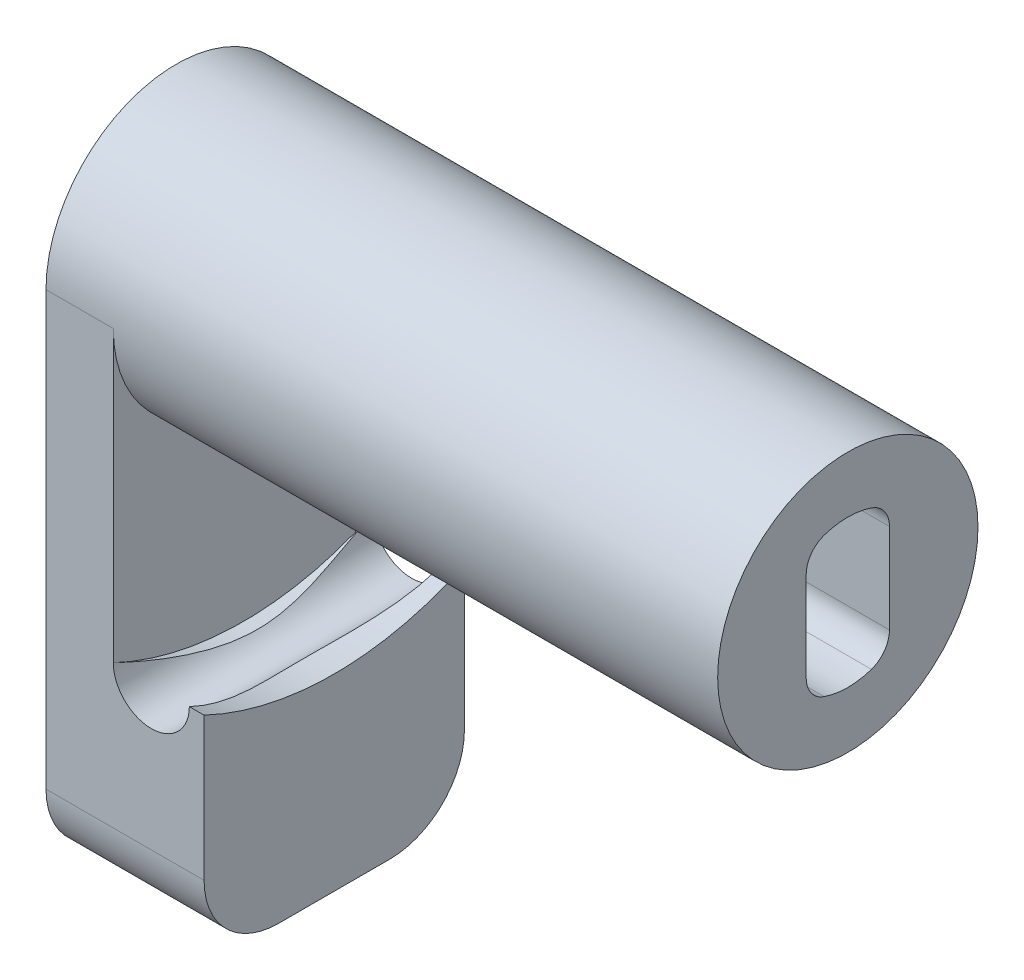
SolidWorks part; units mm, degrees
material "ABS"
ref_plane "Front Plane" through (0, 0, 0) normal (1, 0, 0) x (0, 1, 0)
ref_plane "Top Plane" through (0, 0, 0) normal (0, 0, 1) x (0, 1, 0)
ref_plane "Right Plane" through (0, 0, 0) normal (0, 1, 0) x (-1, 0, 0)
sketch "Sketch1" plane through (0, 0, 0) normal (1, 0, 0) x (0, 1, 0)
  circle A2 centre (0, 0) radius 8.7376
  dimension "D3" = 17.4752
extrude "Boss-Extrude1" add sketch "Sketch1" along normal blind 45.085 contours A2 region at (0, 0, 0)
sketch "Sketch10" plane through (0, 0, 0) normal (-1, 0, 0) x (0, -1, 0)
  line L0 (0, 8.7376) -> (34.036, 8.7376)
  line L2 (34.036, 8.7376) -> (34.036, -8.7376)
  line L3 (34.036, -8.7376) -> (0, -8.7376)
  circle A0 centre (0, 0) radius 8.7376 construction
  arc A2 (0, 8.7376) -> (0, -8.7376) centre (0, 0) cw
  dimension "D1" = 34.036
extrude "Boss-Extrude3" add sketch "Sketch10" against normal blind 4.516 contours L0 A2 L3 L2 region at (0, -20.3793, 0)
fillet "Fillet2" radius 5 2 edges at (2.258, -34.036, 8.7376) (2.258, -34.036, -8.7376)
sketch "Sketch14" [suppressed] plane through (0, 0, 0) normal (-1, 0, 0) x (0, 0, 1)
  line L0 (0.5115, -3.4237) -> (0.3944, -4.0089)
  line L1 (0, 0) -> (0, -4.064) construction
  line L2 (0, 0) -> (0.5606, -3.4335) construction
  line L3 (0.6039, -3.4087) -> (0.9011, -3.9262)
  line L4 (-0.6903, -3.3922) -> (-1.0005, -3.9021)
  line L5 (-0.5983, -3.4096) -> (-0.4961, -3.9976)
  line L6 (-1.8089, -2.9515) -> (-2.2748, -3.3245)
  line L7 (-1.7284, -2.9994) -> (-1.8334, -3.5869)
  line L8 (-2.7093, -2.1549) -> (-3.2746, -2.346)
  line L9 (-2.65, -2.2273) -> (-2.9496, -2.7435)
  line L10 (-3.2829, -1.0983) -> (-3.8795, -1.0846)
  line L11 (-3.252, -1.1867) -> (-3.7101, -1.5692)
  line L12 (-3.4605, 0.0907) -> (-4.0165, 0.3077)
  line L13 (-3.4617, -0.0029) -> (-4.023, -0.2057)
  line L14 (-3.2208, 1.2689) -> (-3.669, 1.6629)
  line L15 (-3.2539, 1.1813) -> (-3.8507, 1.1827)
  line L16 (-2.5926, 2.2939) -> (-2.879, 2.8175)
  line L17 (-2.6537, 2.223) -> (-3.214, 2.4284)
  line L18 (-1.6517, 3.0423) -> (-1.7417, 3.6323)
  line L19 (-1.7333, 2.9965) -> (-2.1896, 3.3812)
  line L20 (-0.5115, 3.4237) -> (-0.3944, 4.0089)
  line L21 (-0.6039, 3.4087) -> (-0.9011, 3.9262)
  line L22 (0.6903, 3.3922) -> (1.0005, 3.9021)
  line L23 (0.5983, 3.4096) -> (0.4961, 3.9976)
  line L24 (1.8089, 2.9515) -> (2.2748, 3.3245)
  line L25 (1.7284, 2.9994) -> (1.8334, 3.5869)
  line L26 (2.7093, 2.1549) -> (3.2746, 2.346)
  line L27 (2.65, 2.2273) -> (2.9496, 2.7435)
  line L28 (3.2829, 1.0983) -> (3.8795, 1.0846)
  line L29 (3.252, 1.1867) -> (3.7101, 1.5692)
  line L30 (3.4605, -0.0907) -> (4.0165, -0.3077)
  line L31 (3.4617, 0.0029) -> (4.023, 0.2057)
  line L32 (3.2208, -1.2689) -> (3.669, -1.6629)
  line L33 (3.2539, -1.1813) -> (3.8507, -1.1827)
  line L34 (2.5926, -2.2939) -> (2.879, -2.8175)
  line L35 (2.6537, -2.223) -> (3.214, -2.4284)
  line L36 (1.6517, -3.0423) -> (1.7417, -3.6323)
  line L37 (1.7333, -2.9965) -> (2.1896, -3.3812)
  line L38 (-0.1032, -4.0627) -> (0, -4.064)
  line L39 (-1.4865, -3.7824) -> (-1.39, -3.8189)
  line L40 (-2.6905, -3.0459) -> (-2.6123, -3.1132)
  line L41 (-3.5195, -2.032) -> (-3.57, -1.942)
  line L42 (-4.0023, -0.7057) -> (-4.0189, -0.6039)
  line L43 (-4.0023, 0.7057) -> (-3.9831, 0.8071)
  line L44 (-3.5195, 2.032) -> (-3.4668, 2.1207)
  line L45 (-2.6123, 3.1132) -> (-2.5324, 3.1785)
  line L46 (-1.39, 3.8189) -> (-1.2926, 3.853)
  line L47 (0, 4.064) -> (0.1032, 4.0627)
  line L48 (1.39, 3.8189) -> (1.4865, 3.7824)
  line L49 (2.6123, 3.1132) -> (2.6905, 3.0459)
  line L50 (3.5195, 2.032) -> (3.57, 1.942)
  line L51 (4.0023, 0.7057) -> (4.0189, 0.6039)
  line L52 (4.0023, -0.7057) -> (3.9831, -0.8071)
  line L53 (3.5195, -2.032) -> (3.4668, -2.1207)
  line L54 (2.6123, -3.1132) -> (2.5324, -3.1785)
  line L55 (1.39, -3.8189) -> (1.2926, -3.853)
  arc A0 (0.3497, -4.0489) -> (0, -4.064) centre (0, 0) cw
  arc A1 (0.3497, -4.0489) -> (0.3944, -4.0089) centre (0.3454, -3.9991) ccw
  arc A2 (0.5115, -3.4237) -> (0.6039, -3.4087) centre (0.5606, -3.4335) cw
  arc A3 (0.4203, -4.0631) -> (0.3944, -4.0089) centre (0.4434, -4.0187) cw
  arc A4 (0.4203, -4.0631) -> (0.7372, -4.2116) centre (2.3016, -0.4608) ccw
  arc A6 (0.9562, -3.9499) -> (0.9011, -3.9262) centre (0.9445, -3.9013) cw
  arc A7 (0.9562, -3.9499) -> (1.2926, -3.853) centre (0, 0) ccw
  arc A8 (-1.0562, -3.9243) -> (-1.39, -3.8189) centre (0, 0) cw
  arc A9 (-1.0562, -3.9243) -> (-1.0005, -3.9021) centre (-1.0432, -3.8761) ccw
  arc A10 (-0.6903, -3.3922) -> (-0.5983, -3.4096) centre (-0.6476, -3.4182) cw
  arc A11 (-0.4524, -4.0387) -> (-0.4961, -3.9976) centre (-0.4468, -3.9891) cw
  arc A12 (-0.4524, -4.0387) -> (-0.1032, -4.0627) centre (0, 0) ccw
  arc A13 (-2.3347, -3.3264) -> (-2.6123, -3.1132) centre (0, 0) cw
  arc A14 (-2.3347, -3.3264) -> (-2.2748, -3.3245) centre (-2.306, -3.2855) ccw
  arc A15 (-1.8089, -2.9515) -> (-1.7284, -2.9994) centre (-1.7776, -2.9906) cw
  arc A16 (-1.8064, -3.6405) -> (-1.8334, -3.5869) centre (-1.7842, -3.5957) cw
  arc A17 (-1.8064, -3.6405) -> (-1.4865, -3.7824) centre (0, 0) ccw
  arc A18 (-3.3316, -2.3273) -> (-3.5195, -2.032) centre (0, 0) cw
  arc A19 (-3.3316, -2.3273) -> (-3.2746, -2.346) centre (-3.2906, -2.2987) ccw
  arc A20 (-2.7093, -2.1549) -> (-2.65, -2.2273) centre (-2.6933, -2.2022) cw
  arc A21 (-2.9426, -2.8031) -> (-2.9496, -2.7435) centre (-2.9064, -2.7686) cw
  arc A22 (-2.9426, -2.8031) -> (-2.6905, -3.0459) centre (0, 0) ccw
  arc A23 (-3.9267, -1.0475) -> (-4.0023, -0.7057) centre (0, 0) cw
  arc A24 (-3.9267, -1.0475) -> (-3.8795, -1.0846) centre (-3.8784, -1.0346) ccw
  arc A25 (-3.2829, -1.0983) -> (-3.252, -1.1867) centre (-3.284, -1.1483) cw
  arc A26 (-3.7238, -1.6276) -> (-3.7101, -1.5692) centre (-3.678, -1.6076) cw
  arc A27 (-3.7238, -1.6276) -> (-3.57, -1.942) centre (0, 0) ccw
  arc A28 (-4.0481, 0.3587) -> (-4.0023, 0.7057) centre (0, 0) cw
  arc A29 (-4.0481, 0.3587) -> (-4.0165, 0.3077) centre (-3.9983, 0.3543) ccw
  arc A30 (-3.4605, 0.0907) -> (-3.4617, -0.0029) centre (-3.4787, 0.0442) cw
  arc A31 (-4.0559, -0.2558) -> (-4.023, -0.2057) centre (-4.006, -0.2527) cw
  arc A32 (-4.0559, -0.2558) -> (-4.0189, -0.6039) centre (0, 0) ccw
  arc A33 (-3.6813, 1.7216) -> (-3.5195, 2.032) centre (0, 0) cw
  arc A34 (-3.6813, 1.7216) -> (-3.669, 1.6629) centre (-3.636, 1.7005) ccw
  arc A35 (-3.2208, 1.2689) -> (-3.2539, 1.1813) centre (-3.2538, 1.2313) cw
  arc A36 (-3.8988, 1.1468) -> (-3.8507, 1.1827) centre (-3.8509, 1.1327) cw
  arc A37 (-3.8988, 1.1468) -> (-3.9831, 0.8071) centre (0, 0) ccw
  arc A38 (-2.8705, 2.8769) -> (-2.6123, 3.1132) centre (0, 0) cw
  arc A39 (-2.8705, 2.8769) -> (-2.879, 2.8175) centre (-2.8352, 2.8415) ccw
  arc A40 (-2.5926, 2.2939) -> (-2.6537, 2.223) centre (-2.6365, 2.2699) cw
  arc A41 (-3.2715, 2.4111) -> (-3.214, 2.4284) centre (-3.2312, 2.3815) cw
  arc A42 (-3.2715, 2.4111) -> (-3.4668, 2.1207) centre (0, 0) ccw
  arc A43 (-1.7134, 3.6852) -> (-1.39, 3.8189) centre (0, 0) cw
  arc A44 (-1.7134, 3.6852) -> (-1.7417, 3.6323) centre (-1.6923, 3.6398) ccw
  arc A45 (-1.6517, 3.0423) -> (-1.7333, 2.9965) centre (-1.7011, 3.0348) cw
  arc A46 (-2.2495, 3.3846) -> (-2.1896, 3.3812) centre (-2.2218, 3.343) cw
  arc A47 (-2.2495, 3.3846) -> (-2.5324, 3.1785) centre (0, 0) ccw
  arc A48 (-0.3497, 4.0489) -> (0, 4.064) centre (0, 0) cw
  arc A49 (-0.3497, 4.0489) -> (-0.3944, 4.0089) centre (-0.3454, 3.9991) ccw
  arc A50 (-0.5115, 3.4237) -> (-0.6039, 3.4087) centre (-0.5606, 3.4335) cw
  arc A51 (-0.9562, 3.9499) -> (-0.9011, 3.9262) centre (-0.9445, 3.9013) cw
  arc A52 (-0.9562, 3.9499) -> (-1.2926, 3.853) centre (0, 0) ccw
  arc A53 (1.0562, 3.9243) -> (1.39, 3.8189) centre (0, 0) cw
  arc A54 (1.0562, 3.9243) -> (1.0005, 3.9021) centre (1.0432, 3.8761) ccw
  arc A55 (0.6903, 3.3922) -> (0.5983, 3.4096) centre (0.6476, 3.4182) cw
  arc A56 (0.4524, 4.0387) -> (0.4961, 3.9976) centre (0.4468, 3.9891) cw
  arc A57 (0.4524, 4.0387) -> (0.1032, 4.0627) centre (0, 0) ccw
  arc A58 (2.3347, 3.3264) -> (2.6123, 3.1132) centre (0, 0) cw
  arc A59 (2.3347, 3.3264) -> (2.2748, 3.3245) centre (2.306, 3.2855) ccw
  arc A60 (1.8089, 2.9515) -> (1.7284, 2.9994) centre (1.7776, 2.9906) cw
  arc A61 (1.8064, 3.6405) -> (1.8334, 3.5869) centre (1.7842, 3.5957) cw
  arc A62 (1.8064, 3.6405) -> (1.4865, 3.7824) centre (0, 0) ccw
  arc A63 (3.3316, 2.3273) -> (3.5195, 2.032) centre (0, 0) cw
  arc A64 (3.3316, 2.3273) -> (3.2746, 2.346) centre (3.2906, 2.2987) ccw
  arc A65 (2.7093, 2.1549) -> (2.65, 2.2273) centre (2.6933, 2.2022) cw
  arc A66 (2.9426, 2.8031) -> (2.9496, 2.7435) centre (2.9064, 2.7686) cw
  arc A67 (2.9426, 2.8031) -> (2.6905, 3.0459) centre (0, 0) ccw
  arc A68 (3.9267, 1.0475) -> (4.0023, 0.7057) centre (0, 0) cw
  arc A69 (3.9267, 1.0475) -> (3.8795, 1.0846) centre (3.8784, 1.0346) ccw
  arc A70 (3.2829, 1.0983) -> (3.252, 1.1867) centre (3.284, 1.1483) cw
  arc A71 (3.7238, 1.6276) -> (3.7101, 1.5692) centre (3.678, 1.6076) cw
  arc A72 (3.7238, 1.6276) -> (3.57, 1.942) centre (0, 0) ccw
  arc A73 (4.0481, -0.3587) -> (4.0023, -0.7057) centre (0, 0) cw
  arc A74 (4.0481, -0.3587) -> (4.0165, -0.3077) centre (3.9983, -0.3543) ccw
  arc A75 (3.4605, -0.0907) -> (3.4617, 0.0029) centre (3.4787, -0.0442) cw
  arc A76 (4.0559, 0.2558) -> (4.023, 0.2057) centre (4.006, 0.2527) cw
  arc A77 (4.0559, 0.2558) -> (4.0189, 0.6039) centre (0, 0) ccw
  arc A78 (3.6813, -1.7216) -> (3.5195, -2.032) centre (0, 0) cw
  arc A79 (3.6813, -1.7216) -> (3.669, -1.6629) centre (3.636, -1.7005) ccw
  arc A80 (3.2208, -1.2689) -> (3.2539, -1.1813) centre (3.2538, -1.2313) cw
  arc A81 (3.8988, -1.1468) -> (3.8507, -1.1827) centre (3.8509, -1.1327) cw
  arc A82 (3.8988, -1.1468) -> (3.9831, -0.8071) centre (0, 0) ccw
  arc A83 (2.8705, -2.8769) -> (2.6123, -3.1132) centre (0, 0) cw
  arc A84 (2.8705, -2.8769) -> (2.879, -2.8175) centre (2.8352, -2.8415) ccw
  arc A85 (2.5926, -2.2939) -> (2.6537, -2.223) centre (2.6365, -2.2699) cw
  arc A86 (3.2715, -2.4111) -> (3.214, -2.4284) centre (3.2312, -2.3815) cw
  arc A87 (3.2715, -2.4111) -> (3.4668, -2.1207) centre (0, 0) ccw
  arc A88 (1.7134, -3.6852) -> (1.39, -3.8189) centre (0, 0) cw
  arc A89 (1.7134, -3.6852) -> (1.7417, -3.6323) centre (1.6923, -3.6398) ccw
  arc A90 (1.6517, -3.0423) -> (1.7333, -2.9965) centre (1.7011, -3.0348) cw
  arc A91 (2.2495, -3.3846) -> (2.1896, -3.3812) centre (2.2218, -3.343) cw
  arc A92 (2.2495, -3.3846) -> (2.5324, -3.1785) centre (0, 0) ccw
  point P207 (0, 0)
  dimension "D1" = 4.064
  dimension "D2" = 0.05
  dimension "D3" = 0.05
  dimension "D4" = 0.04
  dimension "D5" = 18
  dimension "D6" = 0.5968
  dimension "D8" = 0.35
sketch "Sketch15" plane through (4.516, 0, 0) normal (1, 0, 0) x (0, 1, 0)
  line L1 (-29.036, 8.7376) -> (-18.796, 8.7376)
  line L2 (-18.796, 8.7376) -> (-18.796, -8.7376)
  line L3 (0, 8.7376) -> (-29.036, 8.7376) construction
  line L4 (-29.036, -8.7376) -> (-18.796, -8.7376)
  line L5 (-34.036, 3.7376) -> (-34.036, -3.7376) construction
  line L6 (-34.036, 3.7376) -> (-34.036, -3.7376)
  line L8 (-29.036, -8.7376) -> (0, -8.7376) construction
  line L13 (0, 8.7376) -> (-29.036, 8.7376)
  line L14 (-34.036, 3.7376) -> (-34.036, -3.7376)
  line L15 (-29.036, -8.7376) -> (0, -8.7376)
  line L17 (-34.036, 3.7376) -> (-34.036, -3.7376)
  arc A0 (-29.036, 8.7376) -> (-34.036, 3.7376) centre (-29.036, 3.7376) ccw construction
  arc A1 (-34.036, -3.7376) -> (-29.036, -8.7376) centre (-29.036, -3.7376) ccw construction
  arc A2 (-29.036, 8.7376) -> (-34.036, 3.7376) centre (-29.036, 3.7376) ccw
  arc A3 (-34.036, -3.7376) -> (-29.036, -8.7376) centre (-29.036, -3.7376) ccw
  arc A7 (-29.036, 8.7376) -> (-34.036, 3.7376) centre (-29.036, 3.7376) ccw
  arc A8 (-34.036, -3.7376) -> (-29.036, -8.7376) centre (-29.036, -3.7376) ccw
  arc A9 (0, 8.7376) -> (0, -8.7376) centre (0, 0) ccw
  arc A10 (-29.036, 8.7376) -> (-34.036, 3.7376) centre (-29.036, 3.7376) ccw
  arc A11 (-34.036, -3.7376) -> (-29.036, -8.7376) centre (-29.036, -3.7376) ccw
  arc A12 (0, 8.7376) -> (0, -8.7376) centre (0, 0) ccw
  line M2 (0, 8.7376) -> (-29.036, 8.7376)
  arc M3 (-29.036, 8.7376) -> (-34.036, 3.7376) centre (-29.036, 3.7376) ccw
  line M4 (-34.036, 3.7376) -> (-34.036, -3.7376)
  arc M5 (-34.036, -3.7376) -> (-29.036, -8.7376) centre (-29.036, -3.7376) ccw
  dimension "D1" = 15.24
  dimension "D2" = 0
extrude "Boss-Extrude4" add sketch "Sketch15" along normal blind 6.096 contours M2 M3 M4 M5 region at (4.516, -26.143, 0)
sketch "Sketch21" plane through (10.612, 0, 0) normal (1, 0, 0) x (0, 1, 0)
  line L2 (-18.796, -8.7376) -> (-18.796, 8.7376)
  line L4 (-29.036, 8.7376) -> (-18.796, 8.7376) construction
  line L5 (-19.431, -8.7376) -> (-18.796, -8.7376)
  line L6 (-18.796, 8.7376) -> (-18.796, -8.7376) construction
  line L8 (-18.796, -8.7376) -> (0, -8.7376) construction
  line L14 (-18.796, -8.7376) -> (-18.796, 8.7376) construction
  line L20 (-18.796, 8.7376) -> (-29.036, 8.7376)
  arc A2 (-19.431, -8.7376) -> (-19.431, 8.7376) centre (-1.0855, 0) cw
  dimension "D4" = 20.32
  dimension "D2" = 0.635
  dimension "D3" = 0.635
extrude "Cut-Extrude8" cut sketch "Sketch21" against normal up to surface (6.096 mm away) contours A2 L2 region at (10.612, -19.8652, 0) up to face at (4.516, -11.5824, 0)
sketch "Sketch22" plane through (45.085, 0, 0) normal (1, 0, 0) x (0, 1, 0)
  line L7 (-4.0897, -2.794) -> (4.0897, 2.794) construction
  line L8 (-4.0897, 2.794) -> (4.0897, -2.794) construction
  line L11 (-4.0897, -2.794) -> (4.0897, -2.794)
  line L13 (-4.0897, 2.794) -> (4.0897, 2.794)
  line L15 (-4.0897, -2.794) -> (4.0897, 2.794) construction
  line L16 (-4.0897, 2.794) -> (4.0897, -2.794) construction
  arc A3 (-4.0897, 2.794) -> (-4.0897, -2.794) centre (0, 0) ccw
  arc A4 (4.0897, -2.794) -> (4.0897, 2.794) centre (0, 0) ccw
  dimension "D2" = 9.906
  dimension "D3" = 5.588
extrude "Cut-Extrude10" cut sketch "Sketch22" against normal blind 12.192
fillet "Fillet11" radius 1.778 4 edges at (38.989, 4.0897, -2.794) (38.989, 4.0897, 2.794) (38.989, -4.0897, -2.794) (38.989, -4.0897, 2.794)
sketch "Sketch25" plane through (0, 0, -8.7376) normal (0, 0, -1) x (1, 0, 0)
  line L3 (4.516, 19.431) -> (4.516, 0) construction
  line L4 (4.516, 19.431) -> (10.612, 19.431) construction
  circle A0 centre (7.0687, 19.431) radius 2.5527
  dimension "D1" = 5.1054
extrude "Cut-Extrude14" cut sketch "Sketch25" against normal through all
sketch "Sketch26" plane through (0, 0, 0) normal (-1, 0, 0) x (0, -1, 0)
  line L1 (3.6846, 1.7145) -> (5.5896, 1.7145)
  line L2 (3.6846, 1.7145) -> (3.6846, -1.7145) construction
  line L3 (3.6846, -1.7145) -> (5.5896, -1.7145)
  line L4 (5.5896, 1.7145) -> (5.5896, -1.7145)
  arc A0 (3.6846, 1.7145) -> (3.6846, -1.7145) centre (0, 0) ccw
  dimension "D1" = 8.128
  dimension "D2" = 3.429
  dimension "D3" = 1.905
extrude "Cut-Extrude15" cut sketch "Sketch26" against normal blind 21.59
fillet "Fillet12" radius 0.3969 4 edges at (10.795, -3.6846, 1.7145) (10.795, -5.5896, 1.7145) (10.795, -3.6846, -1.7145) (10.795, -5.5896, -1.7145)
